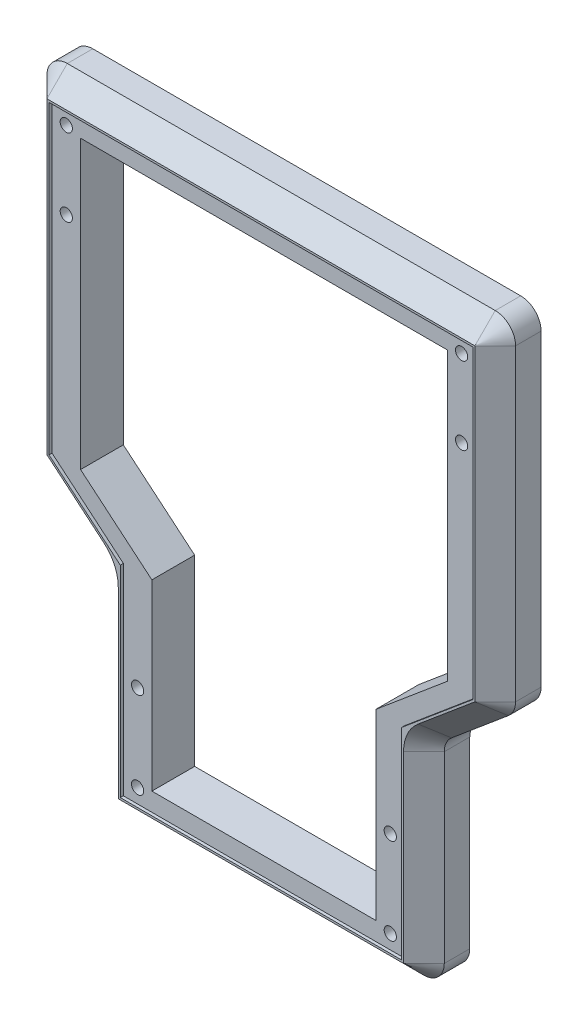
SolidWorks part; units mm, degrees
ref_plane "Plano frontal" through (0, 0, 0) normal (0, 0, 1) x (1, 0, 0)
ref_plane "Plano superior" through (0, 0, 0) normal (0, 1, 0) x (1, 0, 0)
ref_plane "Plano direito" through (0, 0, 0) normal (1, 0, 0) x (0, 0, -1)
sketch "Esboço1" plane through (0, 0, 0) normal (0, 0, 1) x (1, 0, 0)
  line L0 (-70, 0) -> (70, 0)
  line L1 (-80, 10) -> (-80, 100)
  line L2 (-83.5721, 107.6604) -> (-111.4279, 131.0342)
  line L3 (-115, 138.6946) -> (-115, 290)
  line L4 (-105, 300) -> (105, 300)
  line L5 (0, 300) -> (0, 0) construction
  line L6 (115, 138.6946) -> (115, 290)
  line L7 (83.5721, 107.6604) -> (111.4279, 131.0342)
  line L8 (80, 10) -> (80, 100)
  line L9 (-55, 20) -> (55, 20)
  line L10 (-55, 20) -> (-55, 109.7937)
  line L11 (-55, 109.7937) -> (-90, 139.1622)
  line L12 (-90, 139.1622) -> (-90, 280)
  line L13 (90, 139.1622) -> (90, 280)
  line L14 (-90, 280) -> (90, 280)
  line L15 (55, 109.7937) -> (90, 139.1622)
  line L16 (55, 20) -> (55, 109.7937)
  line L17 (115, 138.6946) -> (115, 290)
  line L18 (83.5721, 107.6604) -> (111.4279, 131.0342)
  line L19 (80, 10) -> (80, 100)
  arc A0 (-115, 290) -> (-105, 300) centre (-105, 290) cw
  arc A1 (-111.4279, 131.0342) -> (-115, 138.6946) centre (-105, 138.6946) cw
  arc A2 (-80, 100) -> (-83.5721, 107.6604) centre (-90, 100) ccw
  arc A3 (-70, 0) -> (-80, 10) centre (-70, 10) cw
  arc A4 (70, 0) -> (80, 10) centre (70, 10) ccw
  arc A5 (80, 100) -> (83.5721, 107.6604) centre (90, 100) cw
  arc A6 (111.4279, 131.0342) -> (115, 138.6946) centre (105, 138.6946) ccw
  arc A7 (115, 290) -> (105, 300) centre (105, 290) ccw
  arc A16 (70, 0) -> (80, 10) centre (70, 10) ccw
  arc A17 (80, 100) -> (83.5721, 107.6604) centre (90, 100) cw
  arc A18 (111.4279, 131.0342) -> (115, 138.6946) centre (105, 138.6946) ccw
  arc A19 (115, 290) -> (105, 300) centre (105, 290) ccw
  point P33 (0, 20)
  point P53 (0, 280)
  dimension "D1" = 10
  dimension "D2" = 115
  dimension "D3" = 300
  dimension "D4" = 80
  dimension "D5" = 90
  dimension "D6" = 50
  dimension "D8" = 20
  dimension "D9" = 20
  dimension "D10" = 25
  dimension "D11" = 20
  dimension "D12" = 25
extrude "Ressalto-extrusão1" add sketch "Esboço1" along normal mid plane 45 contours L5 L4 A0 L3 A1 L2 A2 L1 A3 L0 L9 L10 L11 L12 L14 | L4 L5 L14 L13 L15 L16 L9 L0 A4 L8 A5 L7 A6 L6 A7 region at (-74.7992, 5.2008, 0) region at (3.2129, 10, 0)
chamfer "Chanfro1" distance 10 angle 45 32 edges at (80, 55, 22.5) (77.0711, 2.9289, 22.5) (80.9369, 104.2262, 22.5) (0, 0, 22.5) (97.5, 119.3473, 22.5) (-77.0711, 2.9289, 22.5) (114.0631, 134.4685, 22.5) (-80, 55, 22.5) (115, 214.3473, 22.5) (-80.9369, 104.2262, 22.5) (112.0711, 297.0711, 22.5) (-97.5, 119.3473, 22.5) (0, 300, 22.5) (-114.0631, 134.4685, 22.5) (-112.0711, 297.0711, 22.5) (-115, 214.3473, 22.5) (80, 55, -22.5) (77.0711, 2.9289, -22.5) (80.9369, 104.2262, -22.5) (0, 0, -22.5) (97.5, 119.3473, -22.5) (-77.0711, 2.9289, -22.5) (114.0631, 134.4685, -22.5) (-80, 55, -22.5) (115, 214.3473, -22.5) (-80.9369, 104.2262, -22.5) (112.0711, 297.0711, -22.5) (-97.5, 119.3473, -22.5) (0, 300, -22.5) (-114.0631, 134.4685, -22.5) (-112.0711, 297.0711, -22.5) (-115, 214.3473, -22.5)
sketch "Esboço3" plane through (0, 0, 0) normal (0, 0, 1) x (1, 0, 0)
  line L1 (-722.7729, 507.4347) -> (416.458, 507.4347)
  line L2 (-722.7729, 507.4347) -> (-722.7729, -202.3634)
  line L3 (-722.7729, -202.3634) -> (416.458, -202.3634)
  line L4 (416.458, 507.4347) -> (416.458, -202.3634)
extrude "Corte-extrusão1" cut sketch "Esboço3" against normal up to next
sketch "Esboço4" plane through (0, 0, 22.5) normal (0, 0, 1) x (1, 0, 0)
  line L0 (-90, 280) -> (-90, 139.1622)
  line L1 (-55, 109.7937) -> (-90, 139.1622)
  line L2 (-55, 109.7937) -> (-90, 139.1622) construction
  line L3 (-55, 20) -> (-55, 109.7937)
  line L4 (-55, 20) -> (-55, 109.7937) construction
  line L5 (0, -6.7811) -> (0, 343.2781) construction
  line L6 (90, 280) -> (-90, 280)
  line L7 (-55, 20) -> (0, 20)
  line L8 (-90, 280) -> (90, 280) construction
  line L9 (-90, 139.1622) -> (-90, 280) construction
  line L10 (-55, 20) -> (55, 20) construction
  line L13 (104, 289) -> (-104, 289)
  line L14 (-104, 289) -> (-104, 139.1609)
  line L15 (-104, 139.1609) -> (-69, 109.7925)
  line L16 (-69, 109.7925) -> (-69, 11)
  line L17 (-69, 11) -> (69, 11)
  line L20 (69, 109.7925) -> (69, 11)
  line L21 (104, 139.1609) -> (69, 109.7925)
  line L22 (104, 289) -> (104, 139.1609)
  line L23 (55, 20) -> (0, 20)
  line L24 (55, 20) -> (55, 109.7937)
  line L25 (55, 109.7937) -> (90, 139.1622)
  line L26 (90, 280) -> (90, 139.1622)
  dimension "D1" = 9
  dimension "D2" = 14
  dimension "D3" = 9
  dimension "D4" = 14
  dimension "D5" = 9
extrude "Corte-extrusão5" cut sketch "Esboço4" against normal blind 1.5
sketch "Esboço5" plane through (0, 0, 21) normal (0, 0, 1) x (1, 0, 0)
  line L0 (104, 289) -> (-104, 289) construction
  line L1 (-104, 289) -> (-104, 139.1609) construction
  line L2 (-69, 109.7925) -> (-69, 11) construction
  line L3 (0, -34.4878) -> (0, 335.3959) construction
  line L4 (104, 289) -> (-104, 289) construction
  line L5 (-104, 289) -> (-104, 139.1609) construction
  line L6 (-69, 11) -> (69, 11) construction
  circle A0 centre (-97, 244) radius 3
  circle A1 centre (-62, 60.3962) radius 3
  circle A2 centre (-97, 282) radius 3
  circle A3 centre (-62, 18) radius 3
  circle A4 centre (62, 18) radius 3
  circle A5 centre (97, 282) radius 3
  circle A6 centre (62, 60.3962) radius 3
  circle A7 centre (97, 244) radius 3
  dimension "D1" = 45
  dimension "D3" = 7
  dimension "D4" = 7
  dimension "D5" = 7
  dimension "D6" = 7
  dimension "D2" = 7
extrude "Corte-extrusão6" cut sketch "Esboço5" against normal through all
sketch "Esboço7" plane through (0, 0, 0) normal (0, 0, -1) x (-1, 0, 0)
  line L1 (-96.2236, 288.0602) -> (-101.8601, 285.7024)
  line L2 (-101.8601, 285.7024) -> (-102.6365, 279.6422)
  line L3 (-102.6365, 279.6422) -> (-97.7764, 275.9398)
  line L4 (-97.7764, 275.9398) -> (-92.1399, 278.2976)
  line L5 (-92.1399, 278.2976) -> (-91.3635, 284.3578)
  line L6 (-91.3635, 284.3578) -> (-96.2236, 288.0602)
  line L7 (-96.739, 247.9173) -> (-100.262, 246.1847)
  line L8 (-100.262, 246.1847) -> (-100.523, 242.2674)
  line L9 (-100.523, 242.2674) -> (-97.261, 240.0827)
  line L10 (-97.261, 240.0827) -> (-93.738, 241.8153)
  line L11 (-93.738, 241.8153) -> (-93.477, 245.7326)
  line L12 (-93.477, 245.7326) -> (-96.739, 247.9173)
  line L13 (-62, 64.3222) -> (-65.4, 62.3592)
  line L14 (-65.4, 62.3592) -> (-65.4, 58.4332)
  line L15 (-65.4, 58.4332) -> (-62, 56.4702)
  line L16 (-62, 56.4702) -> (-58.6, 58.4332)
  line L17 (-58.6, 58.4332) -> (-58.6, 62.3592)
  line L18 (-58.6, 62.3592) -> (-62, 64.3222)
  line L19 (-62, 19.926) -> (-63.6679, 18.963)
  line L20 (-63.6679, 18.963) -> (-63.6679, 17.037)
  line L21 (-63.6679, 17.037) -> (-62, 16.074)
  line L22 (-62, 16.074) -> (-60.3321, 17.037)
  line L23 (-60.3321, 17.037) -> (-60.3321, 18.963)
  line L24 (-60.3321, 18.963) -> (-62, 19.926)
  line L25 (62.7279, 19.5613) -> (61.0118, 19.4111)
  line L26 (61.0118, 19.4111) -> (60.2839, 17.8498)
  line L27 (60.2839, 17.8498) -> (61.2721, 16.4387)
  line L28 (61.2721, 16.4387) -> (62.9882, 16.5889)
  line L29 (62.9882, 16.5889) -> (63.7161, 18.1502)
  line L30 (63.7161, 18.1502) -> (62.7279, 19.5613)
  line L31 (62, 64.3222) -> (58.6, 62.3592)
  line L32 (58.6, 62.3592) -> (58.6, 58.4332)
  line L33 (58.6, 58.4332) -> (62, 56.4702)
  line L34 (62, 56.4702) -> (65.4, 58.4332)
  line L35 (65.4, 58.4332) -> (65.4, 62.3592)
  line L36 (65.4, 62.3592) -> (62, 64.3222)
  line L37 (97, 247.926) -> (93.6, 245.963)
  line L38 (93.6, 245.963) -> (93.6, 242.037)
  line L39 (93.6, 242.037) -> (97, 240.074)
  line L40 (97, 240.074) -> (100.4, 242.037)
  line L41 (100.4, 242.037) -> (100.4, 245.963)
  line L42 (100.4, 245.963) -> (97, 247.926)
  line L43 (97, 287.926) -> (91.8679, 284.963)
  line L44 (91.8679, 284.963) -> (91.8679, 279.037)
  line L45 (91.8679, 279.037) -> (97, 276.074)
  line L46 (97, 276.074) -> (102.1321, 279.037)
  line L47 (102.1321, 279.037) -> (102.1321, 284.963)
  line L48 (102.1321, 284.963) -> (97, 287.926)
  circle A0 centre (-97, 282) radius 5.2912 construction
  circle A1 centre (-97, 244) radius 3.4 construction
  circle A2 centre (-62, 60.3962) radius 3.4 construction
  circle A3 centre (-62, 18) radius 1.6679 construction
  circle A4 centre (62, 18) radius 1.4919 construction
  circle A5 centre (62, 60.3962) radius 3.4 construction
  circle A6 centre (97, 244) radius 3.4 construction
  circle A7 centre (97, 282) radius 5.1321 construction
extrude "Corte-extrusão8" cut sketch "Esboço7" against normal blind 10
